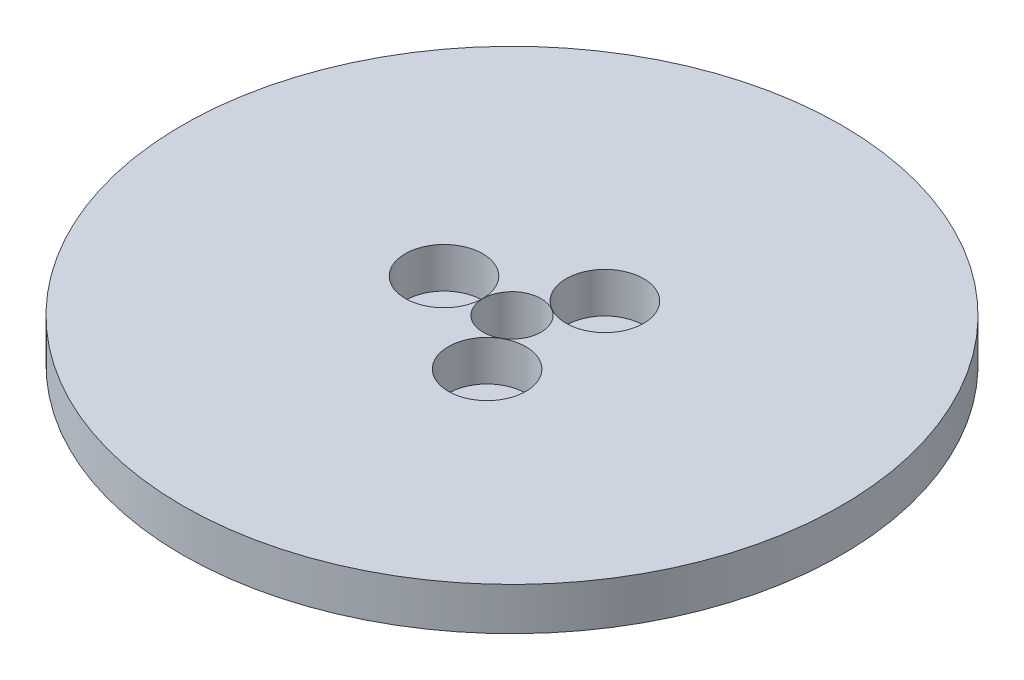
SolidWorks part; units mm, degrees
ref_plane "Front Plane" through (0, 0, 0) normal (0, 0, 1) x (1, 0, 0)
ref_plane "Top Plane" through (0, 0, 0) normal (0, 1, 0) x (1, 0, 0)
ref_plane "Right Plane" through (0, 0, 0) normal (1, 0, 0) x (0, 0, -1)
sketch "Sketch1" plane through (0, 0, 0) normal (0, 1, 0) x (1, 0, 0)
  circle A0 centre (0, 0) radius 85
  dimension "FLANGE_OD" = 170
extrude "Boss-Extrude1" add sketch "Sketch1" along normal blind 11
sketch "Sketch2" plane through (0, 0, 0) normal (0, 1, 0) x (1, 0, 0)
  circle A0 centre (0, 0) radius 7.5
  dimension "BORE_D" = 15
extrude "Cut-Extrude1" cut sketch "Sketch2" along normal through all
sketch "Sketch3" plane through (0, 11, 0) normal (0, 1, 0) x (1, 0, 0)
  circle A0 centre (0, 0) radius 17.54 construction
  circle A1 centre (-17.54, 0) radius 10
  dimension "BOLT_D" = 20
  dimension "BOLT_PCD" = 35.0799
extrude "Cut-Extrude2" cut sketch "Sketch3" against normal blind 10.4121
pattern_circular "CirPattern1" count 3 over 360 about axis through (0, 0, 0) along (0, 1, 0) of "Cut-Extrude2"
